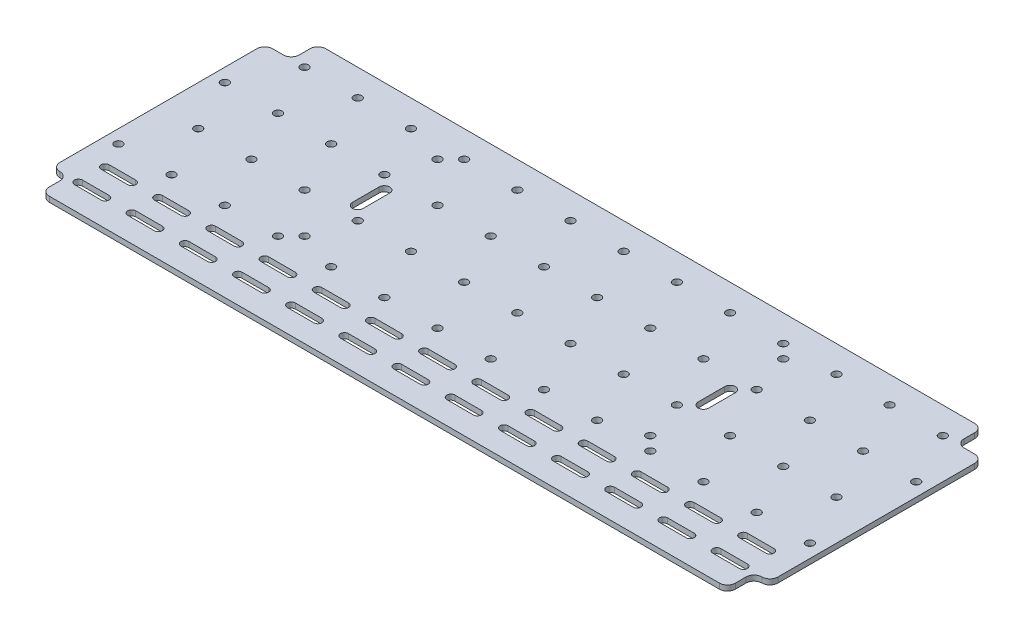
SolidWorks part; units mm, degrees
ref_plane "前视基准面" through (0, 0, 0) normal (0, 0, 1) x (1, 0, 0)
ref_plane "上视基准面" through (0, 0, 0) normal (0, 1, 0) x (1, 0, 0)
ref_plane "右视基准面" through (0, 0, 0) normal (1, 0, 0) x (0, 0, -1)
other "Configuration Table"
sketch "草图1" plane through (0, 0, 0) normal (0, 1, 0) x (1, 0, 0)
  line L1 (-135, 50) -> (135, 50)
  line L2 (-135, 50) -> (-135, -50)
  line L3 (-135, -50) -> (135, -50)
  line L4 (135, 50) -> (135, -50)
  line L5 (-135, 50) -> (135, -50) construction
  line L6 (-135, -50) -> (135, 50) construction
  point P6 (0, 0)
  dimension "D1" = 100
  dimension "D2" = 270
extrude "凸台-拉伸1" add sketch "草图1" along normal blind 2
sketch "草图2" plane through (0, 0, 0) normal (0, -1, 0) x (1, 0, 0)
  line L0 (135, 40) -> (129, 40)
  line L5 (0, 0) -> (0, -35) construction
  line L6 (135, -40) -> (125, -40)
  line L7 (-135, -50) -> (-125, -50)
  line L8 (-135, -50) -> (-135, -40)
  line L9 (-135, -40) -> (-125, -40)
  line L10 (-125, -50) -> (-125, -40)
  line L11 (125, -50) -> (125, -40)
  line L12 (135, -50) -> (125, -50)
  line L13 (135, -50) -> (135, -40)
  line L14 (-135, 50) -> (-129, 50)
  line L15 (-135, 50) -> (-135, 40)
  line L16 (-135, 40) -> (-129, 40)
  line L17 (-129, 50) -> (-129, 40)
  line L18 (129, 50) -> (129, 40)
  line L19 (135, 50) -> (129, 50)
  line L20 (135, 50) -> (135, 40)
  dimension "D1" = 6
  dimension "D2" = 10
  dimension "D3" = 10
  dimension "D4" = 10
extrude "切除-拉伸1" cut sketch "草图2" against normal blind 10
fillet "圆角1" radius 3 12 edges at (-125, 1, -40) (-125, 1, -50) (125, 1, -50) (125, 1, -40) (135, 1, -40) (-135, 1, -40) (129, 1, 40) (129, 1, 50) (-129, 1, 50) (-129, 1, 40) (135, 1, 40) (-135, 1, 40)
sketch "草图3" plane through (0, 0, 0) normal (0, -1, 0) x (1, 0, 0)
  line L0 (0, -50) -> (0, 0) construction
  line L1 (122, -50) -> (-122, -50) construction
  line L2 (-65, 50) -> (-65, -50) construction
  line L3 (-126, 50) -> (126, 50) construction
  line L4 (0, 0) -> (-65, 0) construction
  line L5 (-65, -5) -> (-65, -15) construction
  line L6 (-63, -5) -> (-63, -15)
  line L7 (-67, -5) -> (-67, -15)
  line L8 (65, -5) -> (65, -15) construction
  line L9 (63, -5) -> (63, -15)
  line L10 (67, -5) -> (67, -15)
  circle A0 centre (-65, 15) radius 1.5
  circle A1 centre (-65, -35) radius 1.5
  circle A4 centre (65, -35) radius 1.5
  circle A5 centre (65, 15) radius 1.5
  arc A6 (-63, -5) -> (-67, -5) centre (-65, -5) ccw
  arc A7 (-67, -15) -> (-63, -15) centre (-65, -15) ccw
  arc A8 (63, -5) -> (67, -5) centre (65, -5) cw
  arc A9 (67, -15) -> (63, -15) centre (65, -15) cw
  point P20 (-65, -10)
  point P28 (65, -10)
  dimension "D1" = 3
  dimension "D6" = 2
  dimension "D2" = 50
  dimension "D3" = 65
  dimension "D4" = 15
  dimension "D5" = 25
  dimension "D7" = 10
extrude "切除-拉伸2" cut sketch "草图3" against normal blind 30
sketch "草图4" plane through (0, 0, 0) normal (0, -1, 0) x (1, 0, 0)
  line L0 (-120, 0) -> (0, 0) construction
  line L1 (-130, -20) -> (-110, -20) construction
  line L2 (-130, -20) -> (-130, 20) construction
  line L3 (-130, 20) -> (-110, 20) construction
  line L4 (-110, -20) -> (-110, 20) construction
  line L5 (-130, -20) -> (-110, 20) construction
  line L6 (-130, 20) -> (-110, -20) construction
  line L7 (-125, 30) -> (-115, 30) construction
  line L8 (-120, 0) -> (-120, -40) construction
  line L9 (-125, 31.5) -> (-115, 31.5)
  line L10 (-120, -40) -> (-100, -40) construction
  line L11 (-90, -20) -> (-70, -20) construction
  line L12 (-90, -20) -> (-90, 20) construction
  line L13 (-90, 20) -> (-70, 20) construction
  line L14 (-70, -20) -> (-70, 20) construction
  line L15 (-90, -20) -> (-70, 20) construction
  line L16 (-90, 20) -> (-70, -20) construction
  line L17 (-125, 28.5) -> (-115, 28.5)
  line L18 (-80, 0) -> (-80, -40) construction
  line L19 (-120, 0) -> (-120, 30) construction
  line L20 (-80, -40) -> (-60, -40) construction
  line L21 (-50, -20) -> (-30, -20) construction
  line L22 (-50, -20) -> (-50, 20) construction
  line L23 (-50, 20) -> (-30, 20) construction
  line L24 (-30, -20) -> (-30, 20) construction
  line L25 (-50, -20) -> (-30, 20) construction
  line L26 (-50, 20) -> (-30, -20) construction
  line L27 (-105, 30) -> (-95, 30) construction
  line L28 (-40, 0) -> (-40, -40) construction
  line L29 (-105, 31.5) -> (-95, 31.5)
  line L30 (-40, -40) -> (-20, -40) construction
  line L31 (-10, -20) -> (10, -20) construction
  line L32 (-10, -20) -> (-10, 20) construction
  line L33 (-10, 20) -> (10, 20) construction
  line L34 (10, -20) -> (10, 20) construction
  line L35 (-10, -20) -> (10, 20) construction
  line L36 (-10, 20) -> (10, -20) construction
  line L37 (-105, 28.5) -> (-95, 28.5)
  line L38 (0, 0) -> (0, -40) construction
  line L39 (-85, 30) -> (-75, 30) construction
  line L40 (0, -40) -> (20, -40) construction
  line L41 (30, -20) -> (50, -20) construction
  line L42 (30, -20) -> (30, 20) construction
  line L43 (30, 20) -> (50, 20) construction
  line L44 (50, -20) -> (50, 20) construction
  line L45 (30, -20) -> (50, 20) construction
  line L46 (30, 20) -> (50, -20) construction
  line L47 (-85, 31.5) -> (-75, 31.5)
  line L48 (40, 0) -> (40, -40) construction
  line L49 (-85, 28.5) -> (-75, 28.5)
  line L50 (40, -40) -> (60, -40) construction
  line L51 (70, -20) -> (90, -20) construction
  line L52 (70, -20) -> (70, 20) construction
  line L53 (70, 20) -> (90, 20) construction
  line L54 (90, -20) -> (90, 20) construction
  line L55 (70, -20) -> (90, 20) construction
  line L56 (70, 20) -> (90, -20) construction
  line L57 (-65, 30) -> (-55, 30) construction
  line L58 (80, 0) -> (80, -40) construction
  line L59 (-65, 31.5) -> (-55, 31.5)
  line L60 (80, -40) -> (100, -40) construction
  line L61 (110, -20) -> (130, -20) construction
  line L62 (110, -20) -> (110, 20) construction
  line L63 (110, 20) -> (130, 20) construction
  line L64 (130, -20) -> (130, 20) construction
  line L65 (110, -20) -> (130, 20) construction
  line L66 (110, 20) -> (130, -20) construction
  line L67 (-65, 28.5) -> (-55, 28.5)
  line L68 (120, 0) -> (120, -40) construction
  line L69 (-45, 30) -> (-35, 30) construction
  line L70 (120, -40) -> (140, -40) construction
  line L71 (-45, 31.5) -> (-35, 31.5)
  line L72 (-45, 28.5) -> (-35, 28.5)
  line L73 (-25, 30) -> (-15, 30) construction
  line L74 (-25, 31.5) -> (-15, 31.5)
  line L75 (-25, 28.5) -> (-15, 28.5)
  line L76 (-5, 30) -> (5, 30) construction
  line L77 (-5, 31.5) -> (5, 31.5)
  line L78 (-5, 28.5) -> (5, 28.5)
  line L79 (15, 30) -> (25, 30) construction
  line L80 (15, 31.5) -> (25, 31.5)
  line L81 (15, 28.5) -> (25, 28.5)
  line L82 (35, 30) -> (45, 30) construction
  line L83 (35, 31.5) -> (45, 31.5)
  line L84 (35, 28.5) -> (45, 28.5)
  line L85 (55, 30) -> (65, 30) construction
  line L86 (55, 31.5) -> (65, 31.5)
  line L87 (55, 28.5) -> (65, 28.5)
  line L88 (75, 30) -> (85, 30) construction
  line L89 (75, 31.5) -> (85, 31.5)
  line L90 (75, 28.5) -> (85, 28.5)
  line L91 (95, 30) -> (105, 30) construction
  line L92 (95, 31.5) -> (105, 31.5)
  line L93 (95, 28.5) -> (105, 28.5)
  line L94 (115, 30) -> (125, 30) construction
  line L95 (115, 31.5) -> (125, 31.5)
  line L96 (115, 28.5) -> (125, 28.5)
  line L97 (0, 0) -> (0, 30) construction
  line L98 (-125, 40) -> (-115, 40) construction
  line L99 (-125, 41.5) -> (-115, 41.5)
  line L100 (-125, 38.5) -> (-115, 38.5)
  line L101 (-105, 40) -> (-95, 40) construction
  line L102 (-105, 41.5) -> (-95, 41.5)
  line L103 (-105, 38.5) -> (-95, 38.5)
  line L104 (-85, 40) -> (-75, 40) construction
  line L105 (-85, 41.5) -> (-75, 41.5)
  line L106 (-85, 38.5) -> (-75, 38.5)
  line L107 (-65, 40) -> (-55, 40) construction
  line L108 (-65, 41.5) -> (-55, 41.5)
  line L109 (-65, 38.5) -> (-55, 38.5)
  line L110 (-45, 40) -> (-35, 40) construction
  line L111 (-45, 41.5) -> (-35, 41.5)
  line L112 (-45, 38.5) -> (-35, 38.5)
  line L113 (-25, 40) -> (-15, 40) construction
  line L114 (-25, 41.5) -> (-15, 41.5)
  line L115 (-25, 38.5) -> (-15, 38.5)
  line L116 (-5, 40) -> (5, 40) construction
  line L117 (-5, 41.5) -> (5, 41.5)
  line L118 (-5, 38.5) -> (5, 38.5)
  line L119 (15, 40) -> (25, 40) construction
  line L120 (15, 41.5) -> (25, 41.5)
  line L121 (15, 38.5) -> (25, 38.5)
  line L122 (35, 40) -> (45, 40) construction
  line L123 (35, 41.5) -> (45, 41.5)
  line L124 (35, 38.5) -> (45, 38.5)
  line L125 (55, 40) -> (65, 40) construction
  line L126 (55, 41.5) -> (65, 41.5)
  line L127 (55, 38.5) -> (65, 38.5)
  line L128 (75, 40) -> (85, 40) construction
  line L129 (75, 41.5) -> (85, 41.5)
  line L130 (75, 38.5) -> (85, 38.5)
  line L131 (95, 40) -> (105, 40) construction
  line L132 (95, 41.5) -> (105, 41.5)
  line L133 (95, 38.5) -> (105, 38.5)
  line L134 (115, 40) -> (125, 40) construction
  line L135 (115, 41.5) -> (125, 41.5)
  line L136 (115, 38.5) -> (125, 38.5)
  arc A6 (-125, 41.5) -> (-125, 38.5) centre (-125, 40) ccw
  circle A7 centre (-130, 20) radius 1.5
  circle A8 centre (-110, 20) radius 1.5
  circle A9 centre (-120, 0) radius 1.5
  circle A10 centre (-130, -20) radius 1.5
  circle A11 centre (-110, -20) radius 1.5
  circle A13 centre (-120, -40) radius 1.5
  circle A14 centre (-100, -40) radius 1.5
  circle A16 centre (-90, 20) radius 1.5
  circle A17 centre (-70, 20) radius 1.5
  circle A18 centre (-80, 0) radius 1.5
  circle A19 centre (-90, -20) radius 1.5
  circle A20 centre (-70, -20) radius 1.5
  circle A22 centre (-80, -40) radius 1.5
  circle A23 centre (-60, -40) radius 1.5
  circle A25 centre (-50, 20) radius 1.5
  circle A26 centre (-30, 20) radius 1.5
  circle A27 centre (-40, 0) radius 1.5
  circle A28 centre (-50, -20) radius 1.5
  circle A29 centre (-30, -20) radius 1.5
  circle A31 centre (-40, -40) radius 1.5
  circle A32 centre (-20, -40) radius 1.5
  circle A34 centre (-10, 20) radius 1.5
  circle A35 centre (10, 20) radius 1.5
  circle A36 centre (0, 0) radius 1.5
  circle A37 centre (-10, -20) radius 1.5
  circle A38 centre (10, -20) radius 1.5
  circle A40 centre (0, -40) radius 1.5
  circle A41 centre (20, -40) radius 1.5
  circle A43 centre (30, 20) radius 1.5
  circle A44 centre (50, 20) radius 1.5
  circle A45 centre (40, 0) radius 1.5
  circle A46 centre (30, -20) radius 1.5
  circle A47 centre (50, -20) radius 1.5
  circle A49 centre (40, -40) radius 1.5
  circle A50 centre (60, -40) radius 1.5
  circle A52 centre (70, 20) radius 1.5
  circle A53 centre (90, 20) radius 1.5
  circle A54 centre (80, 0) radius 1.5
  circle A55 centre (70, -20) radius 1.5
  circle A56 centre (90, -20) radius 1.5
  circle A58 centre (80, -40) radius 1.5
  circle A59 centre (100, -40) radius 1.5
  circle A61 centre (110, 20) radius 1.5
  circle A62 centre (130, 20) radius 1.5
  circle A63 centre (120, 0) radius 1.5
  circle A64 centre (110, -20) radius 1.5
  circle A65 centre (130, -20) radius 1.5
  circle A67 centre (120, -40) radius 1.5
  circle A68 centre (140, -40) radius 1.5
  arc A70 (-125, 31.5) -> (-125, 28.5) centre (-125, 30) ccw
  arc A71 (-115, 28.5) -> (-115, 31.5) centre (-115, 30) ccw
  arc A72 (-105, 31.5) -> (-105, 28.5) centre (-105, 30) ccw
  arc A73 (-95, 28.5) -> (-95, 31.5) centre (-95, 30) ccw
  arc A74 (-85, 31.5) -> (-85, 28.5) centre (-85, 30) ccw
  arc A75 (-75, 28.5) -> (-75, 31.5) centre (-75, 30) ccw
  arc A76 (-65, 31.5) -> (-65, 28.5) centre (-65, 30) ccw
  arc A77 (-55, 28.5) -> (-55, 31.5) centre (-55, 30) ccw
  arc A78 (-45, 31.5) -> (-45, 28.5) centre (-45, 30) ccw
  arc A79 (-35, 28.5) -> (-35, 31.5) centre (-35, 30) ccw
  arc A80 (-25, 31.5) -> (-25, 28.5) centre (-25, 30) ccw
  arc A81 (-15, 28.5) -> (-15, 31.5) centre (-15, 30) ccw
  arc A82 (-5, 31.5) -> (-5, 28.5) centre (-5, 30) ccw
  arc A83 (5, 28.5) -> (5, 31.5) centre (5, 30) ccw
  arc A84 (15, 31.5) -> (15, 28.5) centre (15, 30) ccw
  arc A85 (25, 28.5) -> (25, 31.5) centre (25, 30) ccw
  arc A86 (35, 31.5) -> (35, 28.5) centre (35, 30) ccw
  arc A87 (45, 28.5) -> (45, 31.5) centre (45, 30) ccw
  arc A88 (55, 31.5) -> (55, 28.5) centre (55, 30) ccw
  arc A89 (65, 28.5) -> (65, 31.5) centre (65, 30) ccw
  arc A90 (75, 31.5) -> (75, 28.5) centre (75, 30) ccw
  arc A91 (85, 28.5) -> (85, 31.5) centre (85, 30) ccw
  arc A92 (95, 31.5) -> (95, 28.5) centre (95, 30) ccw
  arc A93 (105, 28.5) -> (105, 31.5) centre (105, 30) ccw
  arc A94 (115, 31.5) -> (115, 28.5) centre (115, 30) ccw
  arc A95 (125, 28.5) -> (125, 31.5) centre (125, 30) ccw
  circle A96 centre (-100, 0) radius 1.5
  circle A97 centre (-60, 0) radius 1.5
  circle A98 centre (-20, 0) radius 1.5
  circle A99 centre (20, 0) radius 1.5
  circle A100 centre (60, 0) radius 1.5
  circle A101 centre (100, 0) radius 1.5
  arc A102 (-115, 38.5) -> (-115, 41.5) centre (-115, 40) ccw
  arc A103 (-105, 41.5) -> (-105, 38.5) centre (-105, 40) ccw
  arc A104 (-95, 38.5) -> (-95, 41.5) centre (-95, 40) ccw
  arc A105 (-85, 41.5) -> (-85, 38.5) centre (-85, 40) ccw
  arc A106 (-75, 38.5) -> (-75, 41.5) centre (-75, 40) ccw
  arc A107 (-65, 41.5) -> (-65, 38.5) centre (-65, 40) ccw
  arc A108 (-55, 38.5) -> (-55, 41.5) centre (-55, 40) ccw
  arc A109 (-45, 41.5) -> (-45, 38.5) centre (-45, 40) ccw
  arc A110 (-35, 38.5) -> (-35, 41.5) centre (-35, 40) ccw
  arc A111 (-25, 41.5) -> (-25, 38.5) centre (-25, 40) ccw
  arc A112 (-15, 38.5) -> (-15, 41.5) centre (-15, 40) ccw
  arc A113 (-5, 41.5) -> (-5, 38.5) centre (-5, 40) ccw
  arc A114 (5, 38.5) -> (5, 41.5) centre (5, 40) ccw
  arc A115 (15, 41.5) -> (15, 38.5) centre (15, 40) ccw
  arc A116 (25, 38.5) -> (25, 41.5) centre (25, 40) ccw
  arc A117 (35, 41.5) -> (35, 38.5) centre (35, 40) ccw
  arc A118 (45, 38.5) -> (45, 41.5) centre (45, 40) ccw
  arc A119 (55, 41.5) -> (55, 38.5) centre (55, 40) ccw
  arc A120 (65, 38.5) -> (65, 41.5) centre (65, 40) ccw
  arc A121 (75, 41.5) -> (75, 38.5) centre (75, 40) ccw
  arc A122 (85, 38.5) -> (85, 41.5) centre (85, 40) ccw
  arc A123 (95, 41.5) -> (95, 38.5) centre (95, 40) ccw
  arc A124 (105, 38.5) -> (105, 41.5) centre (105, 40) ccw
  arc A125 (115, 41.5) -> (115, 38.5) centre (115, 40) ccw
  arc A126 (125, 38.5) -> (125, 41.5) centre (125, 40) ccw
  point P15 (-120, 30)
  point P55 (-100, 30)
  point P82 (-80, 30)
  point P110 (-60, 30)
  point P133 (-40, 30)
  point P140 (-20, 30)
  point P147 (0, 30)
  point P154 (20, 30)
  point P161 (40, 30)
  point P168 (60, 30)
  point P175 (80, 30)
  point P182 (100, 30)
  point P189 (120, 30)
  point P208 (-120, 40)
  point P215 (-100, 40)
  point P222 (-80, 40)
  point P229 (-60, 40)
  point P236 (-40, 40)
  point P243 (-20, 40)
  point P250 (0, 40)
  point P257 (20, 40)
  point P264 (40, 40)
  point P271 (60, 40)
  point P278 (80, 40)
  point P285 (100, 40)
  point P292 (120, 40)
  dimension "D3" = 3
  dimension "D7" = 1.5
  dimension "D1" = 40
  dimension "D2" = 20
  dimension "D4" = 7
  dimension "D5" = 20
  dimension "D6" = 10
  dimension "D8" = 10
  dimension "D10" = 20
  dimension "D12" = 40
  dimension "D14" = 10
  dimension "D9" = 13
  dimension "D11" = 6
  dimension "D13" = 2
extrude "切除-拉伸3" cut sketch "草图4" against normal blind 10
